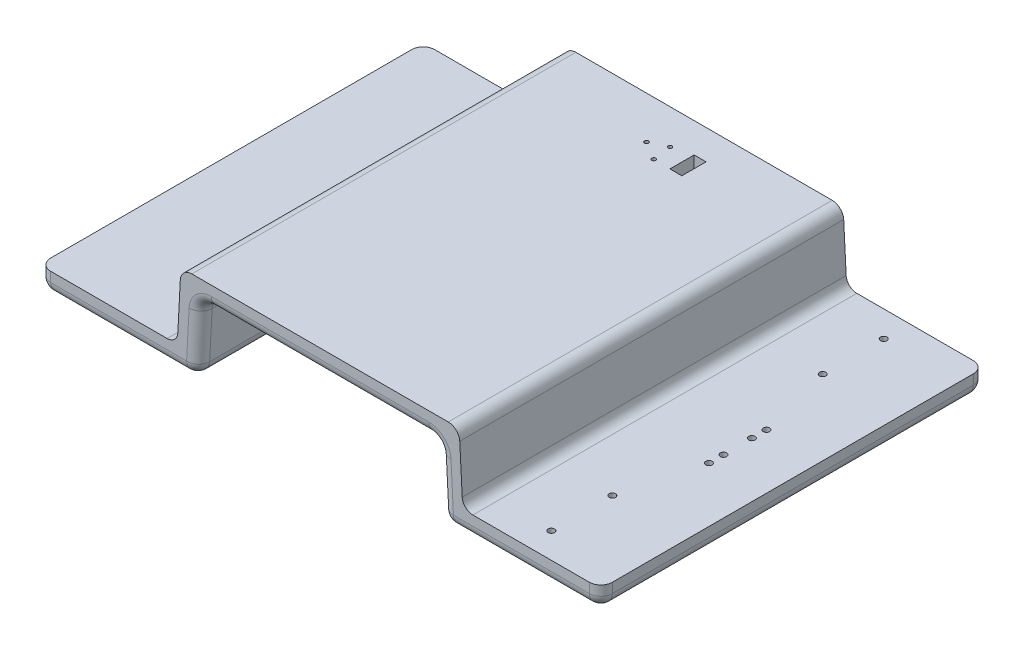
SolidWorks part; units mm, degrees
ref_plane "Front Plane" through (0, 0, 0) normal (0, 0, 1) x (1, 0, 0)
ref_plane "Top Plane" through (0, 0, 0) normal (0, 1, 0) x (1, 0, 0)
ref_plane "Right Plane" through (0, 0, 0) normal (1, 0, 0) x (0, 0, -1)
sketch "Sketch1" plane through (0, 0, 0) normal (0, 0, 1) x (1, 0, 0)
  line L0 (-329.1, -55) -> (-329.1, -80)
  line L1 (-329.1, -80) -> (-156.3657, -80)
  line L2 (-142.8842, -67.2065) -> (-139.9829, -11.8458)
  line L3 (-127.5, 0) -> (127.5, 0)
  line L4 (-329.1, -55) -> (-179.1409, -55)
  line L5 (-166.658, -43.1542) -> (-163.7566, 12.2065)
  line L6 (-150.2751, 25) -> (150.2751, 25)
  line L8 (0, 54.7842) -> (0, -49.5051) construction
  line L9 (166.658, -43.1542) -> (163.7566, 12.2065)
  line L10 (329.1, -55) -> (179.1409, -55)
  line L11 (142.8842, -67.2065) -> (139.9829, -11.8458)
  line L12 (329.1, -80) -> (156.3657, -80)
  line L13 (329.1, -55) -> (329.1, -80)
  arc A0 (-156.3657, -80) -> (-142.8842, -67.2065) centre (-156.3657, -66.5) ccw
  arc A1 (-179.1409, -55) -> (-166.658, -43.1542) centre (-179.1409, -42.5) ccw
  arc A2 (-163.7566, 12.2065) -> (-150.2751, 25) centre (-150.2751, 11.5) cw
  arc A4 (139.9829, -11.8458) -> (127.5, 0) centre (127.5, -12.5) ccw
  arc A5 (163.7566, 12.2065) -> (150.2751, 25) centre (150.2751, 11.5) ccw
  arc A6 (179.1409, -55) -> (166.658, -43.1542) centre (179.1409, -42.5) cw
  arc A7 (156.3657, -80) -> (142.8842, -67.2065) centre (156.3657, -66.5) cw
  arc A8 (-139.9829, -11.8458) -> (-127.5, 0) centre (-127.5, -12.5) cw
  point P9 (0, 25)
  point P10 (0, 0)
  dimension "D7" = 13.5
  dimension "D8" = 12.5
  dimension "D9" = 13.5
  dimension "D11" = 25
  dimension "D2" = 12.5
  dimension "D12" = 12.5
  dimension "D1" = 25
  dimension "D3" = 25
  dimension "D4" = 93
  dimension "D5" = 329.1
  dimension "D6" = 105
  dimension "D10" = 127.5
extrude "Boss-Extrude1" add sketch "Sketch1" along normal blind 225 and the other way blind 225
fillet "Fillet1" radius 13.5 19 edges at (242.7329, -80, -225) (147.0729, -76.2926, -225) (141.4335, -39.5262, -225) (136.1044, -3.4328, -225) (0, 0, -225) (-136.1044, -3.4328, -225) (-141.4335, -39.5262, -225) (-147.0729, -76.2926, -225) (242.7329, -80, 225) (147.0729, -76.2926, 225) (141.4335, -39.5262, 225) (136.1044, -3.4328, 225) (0, 0, 225) (-136.1044, -3.4328, 225) (-141.4335, -39.5262, 225) (-147.0729, -76.2926, 225) (-242.7329, -80, -225) (-329.1, -80, 0) (-242.7329, -80, 225)
fillet "Fillet2" radius 13.5 5 edges at (329.1, -60.75, -225) (329.1, -76.0459, -221.0459) (329.1, -60.75, 225) (329.1, -76.0459, 221.0459) (329.1, -80, 0)
fillet "Fillet3" radius 13.5 4 edges at (-325.1459, -76.0459, -221.0459) (-325.1459, -76.0459, 221.0459) (-329.1, -60.75, -225) (-329.1, -60.75, 225)
sketch "Sketch2" plane through (0, -55, 0) normal (0, 1, 0) x (1, 0, 0)
  circle A0 centre (264.6539, 33.5296) radius 3.75
  circle A1 centre (264.6539, 16.5296) radius 3.75
  circle A2 centre (264.8051, -17) radius 3.75
  circle A3 centre (264.8051, -34) radius 3.75
  circle A4 centre (241.1409, -195) radius 3.75
  circle A5 centre (241.1409, -123.52) radius 3.75
  circle A6 centre (241.1409, 123.0496) radius 3.75
  circle A7 centre (241.1409, 194.5296) radius 3.75
  circle A8 centre (241.1409, 194.5296) radius 3.5 construction
  circle A9 centre (241.1409, 123.0496) radius 3.5 construction
  circle A10 centre (264.6539, 33.5296) radius 3.5 construction
  circle A11 centre (264.6539, 16.5296) radius 3.5 construction
  circle A12 centre (241.1409, -123.52) radius 3.5 construction
  circle A13 centre (241.1409, -195) radius 3.5 construction
  ellipse E0 centre (264.8051, -17) end of major axis (264.8051, -13.5) minor radius 3.4999 construction
  ellipse E1 centre (264.8051, -34) end of major axis (264.8051, -30.5) minor radius 3.4999 construction
extrude "Cut-Extrude1" cut sketch "Sketch2" against normal through all
sketch "Sketch3" plane through (0, 0, 0) normal (0, -1, 0) x (1, 0, 0)
  line L0 (1.4361, -183.8069) -> (0.729, -184.514) construction
  line L1 (23.3347, -161.7211) -> (37.2972, -161.7211)
  line L2 (23.3347, -161.7211) -> (23.3347, -190.1211)
  line L3 (23.3347, -190.1211) -> (37.2972, -190.1211)
  line L4 (37.2972, -161.7211) -> (37.2972, -190.1211)
  circle A0 centre (1.0826, -184.1604) radius 2.2173
  circle A1 centre (4.06, -162.1196) radius 2.287
  circle A2 centre (-17.6244, -175.332) radius 2.375
extrude "Cut-Extrude2" cut sketch "Sketch3" against normal through all
